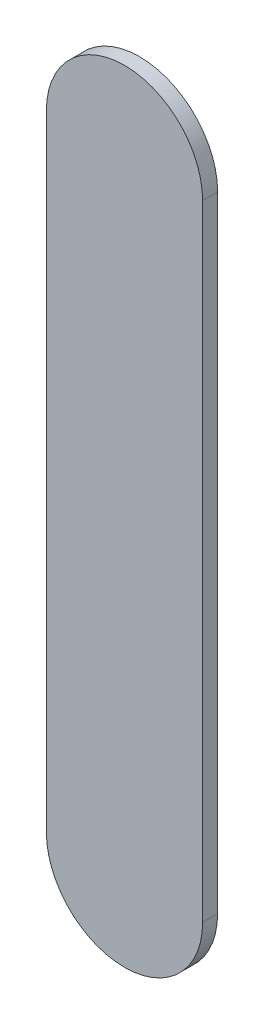
SolidWorks part; units mm, degrees
material "Stainless Steel (ferritic)"
ref_plane "Front Plane" through (0, 0, 0) normal (0, 0, 1) x (1, 0, 0)
ref_plane "Top Plane" through (0, 0, 0) normal (0, 1, 0) x (1, 0, 0)
ref_plane "Right Plane" through (0, 0, 0) normal (1, 0, 0) x (0, 0, -1)
ref_axis "Axis1" through (0, 0, 0) along (0, 1, 0)
sketch "Sketch1" plane through (0, 0, 0) normal (0, 0, 1) x (1, 0, 0)
  line L0 (0, 12.7) -> (0, -12.7) construction
  line L1 (3.175, 12.7) -> (3.175, -12.7)
  line L2 (-3.175, 12.7) -> (-3.175, -12.7)
  arc A0 (3.175, 12.7) -> (-3.175, 12.7) centre (0, 12.7) ccw
  arc A1 (-3.175, -12.7) -> (3.175, -12.7) centre (0, -12.7) ccw
  point P3 (0, 0)
  dimension "D1" = 25.4
  dimension "D2" = 6.35
extrude "Boss-Extrude1" add sketch "Sketch1" along normal blind 0.6096
